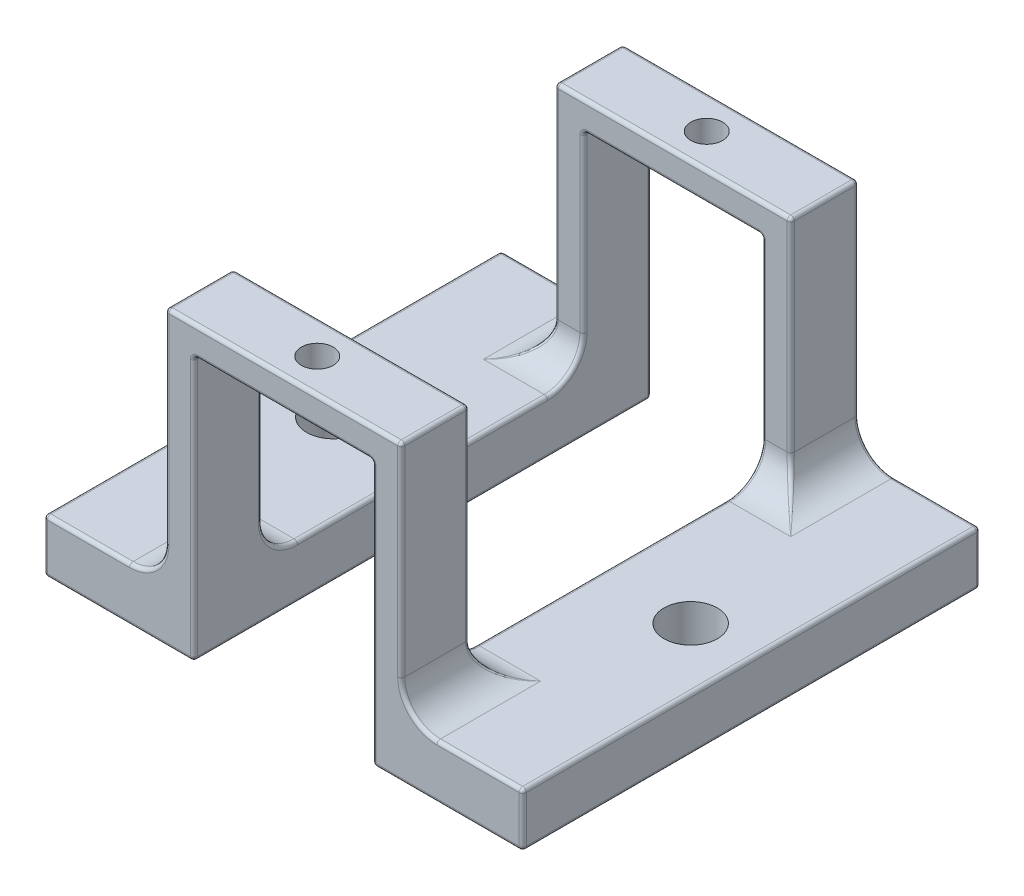
SolidWorks part; units mm, degrees
material "ABS"
ref_plane "Front Plane" through (0, 0, 0) normal (0, 0, 1) x (1, 0, 0)
ref_plane "Top Plane" through (0, 0, 0) normal (0, 1, 0) x (1, 0, 0)
ref_plane "Right Plane" through (0, 0, 0) normal (1, 0, 0) x (0, 0, -1)
sketch "Sketch1" plane through (0, 0, 0) normal (0, 0, 1) x (1, 0, 0)
  line L0 (0, 0) -> (0, 15.748) construction
  line L2 (6.096, 15.748) -> (-6.096, 15.748) construction
  line L3 (-17.018, 0) -> (-6.35, 0)
  line L4 (-27.94, 0) -> (27.94, 0) construction
  line L5 (17.018, 0) -> (6.35, 0)
  line L6 (-6.35, 0) -> (-6.35, 18.796)
  line L7 (6.35, 0) -> (6.35, 18.796)
  line L8 (-6.35, 18.796) -> (6.35, 18.796)
  line L9 (-6.35, 0.254) -> (-6.35, 15.748) construction
  line L10 (-6.096, 18.796) -> (6.096, 18.796) construction
  line L11 (-17.018, 0) -> (-17.018, 3.81)
  line L12 (17.018, 0) -> (17.018, 3.81)
  line L13 (-17.018, 3.81) -> (-8.382, 3.81)
  line L14 (17.018, 3.81) -> (8.382, 3.81)
  line L15 (-8.382, 3.81) -> (-8.382, 20.828)
  line L16 (8.382, 3.81) -> (8.382, 20.828)
  line L17 (-8.382, 20.828) -> (8.382, 20.828)
  line L18 (-6.35, 18.796) -> (-6.35, 20.828) construction
  line L19 (-6.35, 18.796) -> (-8.382, 18.796) construction
  line L20 (-9.525, 0) -> (-15.875, 0) construction
  point P27 (-12.7, 3.81)
  point P28 (-12.7, 0)
  dimension "D1" = 2.032
  dimension "D2" = 3.81
extrude "Boss-Extrude1" add sketch "Sketch1" along normal up to surface (4.826 mm away) and the other way up to surface (27.686 mm away) contours L15 L17 L16 L14 L12 L5 L7 L8 L6 L3 L11 L13
sketch "Sketch2" plane through (-8.382, 0, 0) normal (-1, 0, 0) x (0, 0, 1)
  line L0 (4.826, 20.828) -> (-27.686, 20.828) construction
  line L1 (-22.86, 20.828) -> (0, 20.828)
  line L2 (-22.86, 20.828) -> (-22.86, 3.81)
  line L3 (-22.86, 3.81) -> (0, 3.81)
  line L4 (0, 20.828) -> (0, 3.81)
  line L5 (4.826, 3.81) -> (-27.686, 3.81) construction
  line L6 (0, 22.606) -> (0, 18.796) construction
  line L7 (-22.86, 18.796) -> (-22.86, 22.606) construction
extrude "Cut-Extrude1" cut sketch "Sketch2" against normal through all
fillet "Fillet4" radius 2.54 8 edges at (8.382, 3.81, -25.273) (8.382, 3.81, 2.413) (7.366, 3.81, -22.86) (7.366, 3.81, 0) (-7.366, 3.81, 0) (-8.382, 3.81, 2.413) (-7.366, 3.81, -22.86) (-8.382, 3.81, -25.273)
fillet "Fillet5" radius 0.254 64 edges at (0, 18.796, -27.686) (0, 18.796, 0) (-8.382, 13.589, 0) (6.35, 12.573, 0) (-8.382, 13.589, -27.686) (-9.1259, 4.5539, -22.1161) (-9.1259, 4.5539, -0.7439) (9.1259, 4.5539, -0.7439) (9.1259, 4.5539, -22.1161) (-8.382, 13.589, -22.86) (0, 20.828, 0) (0, 20.828, -22.86) (6.35, 3.81, -11.43) (8.382, 13.589, 0) (0, 18.796, -22.86) (6.35, 12.573, -22.86) (8.382, 13.589, -22.86) (-6.35, 9.398, -27.686) (17.018, 1.905, -27.686) (13.97, 3.81, -27.686) (8.382, 13.589, -27.686) (0, 20.828, -27.686) (-13.97, 3.81, -27.686) (-11.684, 0, 4.826) (-6.35, 9.398, 4.826) (0, 18.796, 4.826) (17.018, 1.905, 4.826) (13.97, 3.81, 4.826) (8.382, 13.589, 4.826) (-8.382, 13.589, 4.826) (-8.382, 20.828, -25.273) (-8.382, 20.828, 2.413) (0, 20.828, 4.826) (8.382, 20.828, -25.273) (8.382, 20.828, 2.413) (17.018, 3.81, -11.43) (17.018, 0, -11.43) (11.684, 0, 4.826) (6.35, 9.398, 4.826) (-6.35, 18.796, -25.273) (-6.35, 18.796, 2.413) (-6.35, 0, -11.43) (-17.018, 1.905, 4.826) (-17.018, 3.81, -11.43) (-13.97, 3.81, 4.826) (-6.35, 3.81, -11.43) (-6.35, 12.573, 0) (-6.35, 12.573, -22.86) (9.1259, 4.5539, -27.686) (9.1259, 4.5539, 4.826) (6.35, 4.5539, -22.1161) (6.35, 4.5539, -0.7439) (-6.35, 4.5539, -0.7439) (-9.1259, 4.5539, 4.826) (-6.35, 4.5539, -22.1161) (-9.1259, 4.5539, -27.686) (11.684, 0, -27.686) (-17.018, 1.905, -27.686) (-11.684, 0, -27.686) (-17.018, 0, -11.43) (6.35, 18.796, 2.413) (6.35, 0, -11.43) (6.35, 9.398, -27.686) (6.35, 18.796, -25.273)
sketch "Sketch4" plane through (0, 3.81, 0) normal (0, 1, 0) x (1, 0, 0)
  line L0 (-17.018, 11.43) -> (-8.382, 11.43) construction
  line L1 (-17.018, -4.572) -> (-17.018, 27.432) construction
  line L3 (8.382, 11.43) -> (17.018, 11.43) construction
  line L5 (17.018, 27.432) -> (17.018, -4.572) construction
  line L6 (-8.382, 27.432) -> (-8.382, 23.114) construction
  line L7 (8.382, 23.114) -> (8.382, 27.432) construction
  point P12 (-12.7, 11.43)
  point P13 (12.7, 11.43)
hole_wizard "#10-24 Tapped Hole1" positions "Sketch6" profile "Sketch5" tap size "#10-24" standard "ANSI Inch" end condition through all
sketch "Sketch6" plane through (0, 3.81, 0) normal (0, 1, 0) x (1, 0, 0)
  point P0 (-12.7, 11.43)
  point P3 (12.7, 11.43)
cosmetic thread "Hole Thread1" parameters "D2"=4.826
cosmetic thread "Hole Thread2" parameters "D2"=4.826
sketch "Sketch5" plane through (-12.7, 3.81, -11.43) normal (1, 0, 0) x (0, 0, 1)
  line L0 (0, 0) -> (0, 3.81)
  line L1 (0, 3.81) -> (1.8986, 3.81)
  line L2 (1.8986, 3.81) -> (1.8986, 0)
  line L5 (1.8986, 0) -> (0, 0)
  line L11 (0, -6.35) -> (0, 107.95) construction
  dimension "Thru Tap Drill Dia." = 3.7973
  dimension "Thru Tap Drill Depth" = 3.81
sketch "Sketch7" plane through (0, 20.828, 0) normal (0, 1, 0) x (1, 0, 0)
  line L0 (0, 27.432) -> (0, 23.114) construction
  line L1 (8.128, 27.432) -> (-8.128, 27.432) construction
  line L2 (-8.128, 23.114) -> (8.128, 23.114) construction
  line L3 (0, -0.254) -> (0, -4.572) construction
  line L4 (8.128, -0.254) -> (-8.128, -0.254) construction
  line L5 (-8.128, -4.572) -> (8.128, -4.572) construction
  point P12 (0, 25.273)
  point P13 (0, -2.413)
hole_wizard "#4-40 Tapped Hole1" positions "Sketch9" profile "Sketch8" tap size "#4-40" standard "ANSI Inch" end condition through all
sketch "Sketch9" plane through (0, 20.828, 0) normal (0, 1, 0) x (1, 0, 0)
  point P0 (0, 25.273)
  point P3 (0, -2.413)
sketch "Sketch8" plane through (0, 20.828, -25.273) normal (1, 0, 0) x (0, 0, 1)
  line L0 (0, 0) -> (0, 20.828)
  line L1 (0, 20.828) -> (1.1303, 20.828)
  line L2 (1.1303, 20.828) -> (1.1303, 0)
  line L5 (1.1303, 0) -> (0, 0)
  line L11 (0, -6.35) -> (0, 107.95) construction
  dimension "Thru Tap Drill Dia." = 2.2606
  dimension "Thru Tap Drill Depth" = 20.828
cosmetic thread "Hole Thread3" parameters "D2"=2.8448
cosmetic thread "Hole Thread4" parameters "D2"=2.8448
